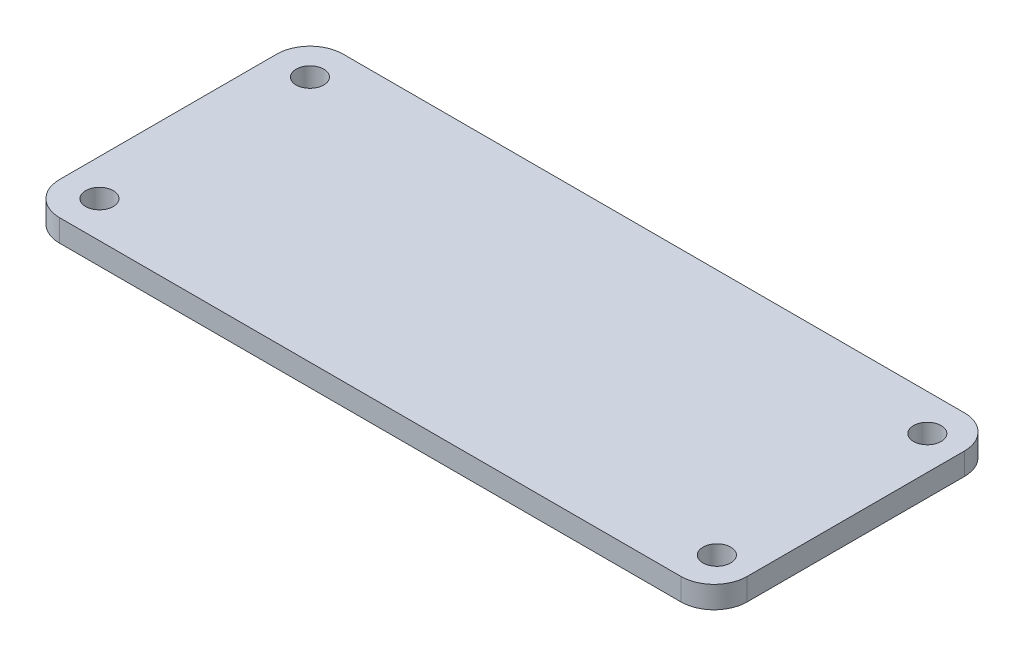
SolidWorks part; units mm, degrees
ref_plane "Front Plane" through (0, 0, 0) normal (0, 0, 1) x (1, 0, 0)
ref_plane "Top Plane" through (0, 0, 0) normal (0, 1, 0) x (1, 0, 0)
ref_plane "Right Plane" through (0, 0, 0) normal (1, 0, 0) x (0, 0, -1)
sketch "Sketch1" plane through (0, 0, 0) normal (0, 1, 0) x (1, 0, 0)
  line L1 (-31.115, 12.827) -> (31.115, 12.827)
  line L2 (-31.115, 12.827) -> (-31.115, -12.827)
  line L3 (-31.115, -12.827) -> (31.115, -12.827)
  line L4 (31.115, 12.827) -> (31.115, -12.827)
  dimension "D1" = 62.23
  dimension "D2" = 25.654
  dimension "D3" = 31.115
  dimension "D4" = 12.827
extrude "Boss-Extrude1" add sketch "Sketch1" along normal blind 2
sketch "Sketch2" plane through (0, 2, 0) normal (0, 1, 0) x (1, 0, 0)
  line L1 (-31.115, -12.827) -> (31.115, -12.827) construction
  line L3 (-31.115, 12.827) -> (-31.115, -12.827) construction
  circle A0 centre (-27.813, 9.525) radius 1.25
  circle A1 centre (28.067, 9.525) radius 1.25
  circle A2 centre (28.067, -9.525) radius 1.25
  circle A3 centre (-27.813, -9.525) radius 1.25
  dimension "D9" = 2.5
  dimension "D10" = 2.5
  dimension "D11" = 2.5
  dimension "D12" = 2.5
  dimension "D2" = 3.302
  dimension "D3" = 3.302
  dimension "D4" = 22.352
  dimension "D5" = 59.182
  dimension "D6" = 59.182
  dimension "D7" = 3.302
  dimension "D8" = 3.302
  dimension "D13" = 22.352
extrude "Cut-Extrude1" cut sketch "Sketch2" against normal blind 2
fillet "Fillet1" radius 3 4 edges at (31.115, 1, 12.827) (31.115, 1, -12.827) (-31.115, 1, -12.827) (-31.115, 1, 12.827)
